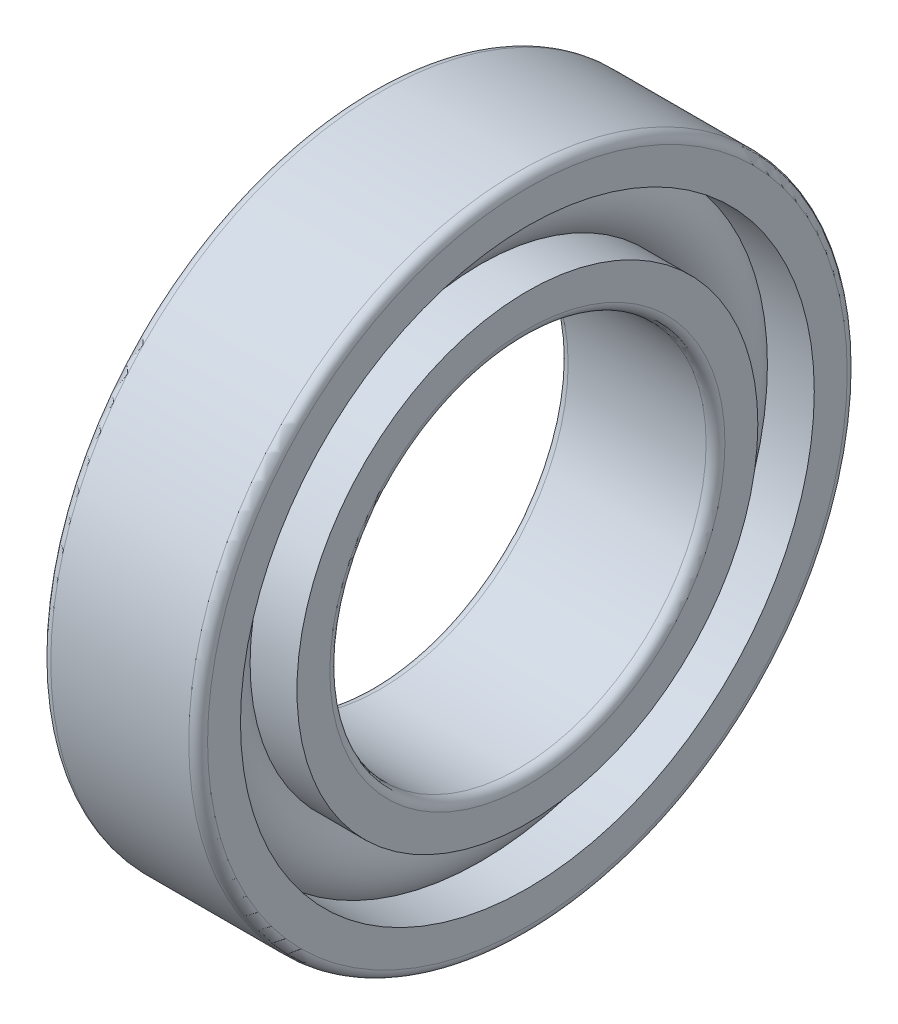
SolidWorks part; units mm, degrees
ref_plane "Plane1" through (0, 0, 0) normal (0, 0, 1) x (1, 0, 0)
ref_plane "Plane2" through (0, 0, 0) normal (0, 1, 0) x (1, 0, 0)
ref_plane "Plane3" through (0, 0, 0) normal (1, 0, 0) x (0, 0, -1)
sketch "Clipboard" plane through (0, 0, 0) normal (0, 0, 1) x (1, 0, 0)
  line L0 (-10, 0) -> (10, 0) construction
  line L1 (0, 0) -> (22.3471, -0.7804)
  line L2 (0, 0) -> (8.245, 0.2879)
  line L3 (0, 0) -> (22.3471, -0.7804)
  line L4 (0, 0) -> (-22.3573, -0.3902)
sketch "CagSpiSke" plane through (0, 0, 0) normal (0, 0, 1) x (1, 0, 0)
  line L0 (0.135, 8.025) -> (0.135, 8.475)
  line L1 (0.135, 8.475) -> (-0.135, 8.475)
  line L2 (-0.135, 8.475) -> (-0.135, 8.025)
  line L3 (-0.135, 8.025) -> (0.135, 8.025)
  line L4 (-20.6375, 0) -> (20.6375, 0) construction
  line L5 (0, 0) -> (0, 23.7692) construction
revolve "CageSpine" add sketch "CagSpiSke" angle 0.001 about L4 reverse direction yes
ref_axis "Axis1" through (-50, 0, 0) along (1, 0, 0)
sketch "CagBalSke" plane through (0, 0, 0) normal (0, 0, 1) x (1, 0, 0)
  line L0 (-1.485, 8.25) -> (1.485, 8.25)
  line L1 (-1.905, 8.25) -> (1.905, 8.25) construction
  line L2 (-10, 0) -> (10, 0) construction
  line L3 (0, 0) -> (0, 24) construction
  arc A0 (1.485, 8.25) -> (-1.485, 8.25) centre (0, 8.25) cw
revolve "CageBall" [suppressed] add sketch "CagBalSke" angle 360 about L1 reverse direction yes
pattern_circular "CageBalls" [suppressed] count 2 every 180 about axis through (-50, 0, 0) along (1, 0, 0)
sketch "CagTrmODSke" plane through (0, 0, 0) normal (0, 0, 1) x (1, 0, 0)
  line L0 (1.486, 8.475) -> (1.486, 9.736)
  line L1 (1.486, 9.736) -> (-1.486, 9.736)
  line L2 (-1.486, 9.736) -> (-1.486, 8.475)
  line L3 (-1.486, 8.475) -> (1.486, 8.475)
  line L4 (-20.6375, 0) -> (20.6375, 0) construction
  line L5 (0, 0) -> (0, 25) construction
revolve "CageTrimOD" [suppressed] cut sketch "CagTrmODSke" angle 360 about L4 reverse direction yes
sketch "CagTrmIDSke" plane through (0, 0, 0) normal (0, 0, 1) x (1, 0, 0)
  line L0 (1.486, 6.766) -> (1.486, 8.025)
  line L1 (1.486, 8.025) -> (-1.486, 8.025)
  line L2 (-1.486, 8.025) -> (-1.486, 6.766)
  line L3 (-1.486, 6.766) -> (1.486, 6.766)
  line L4 (-20.6375, 0) -> (20.6375, 0) construction
  line L5 (0, 0) -> (0, 25) construction
revolve "CageTrimID" [suppressed] cut sketch "CagTrmIDSke" angle 360 about L4 reverse direction yes
sketch "BalSimSke" plane through (0, 0, 0) normal (0, 0, 1) x (1, 0, 0)
  line L0 (-10, 0) -> (10, 0) construction
  line L1 (-10, 8.25) -> (10, 8.25) construction
  line L2 (0, 0) -> (0, 23) construction
  circle A0 centre (0, 8.25) radius 1.35
revolve "BallsSimplified" add sketch "BalSimSke" angle 360 about L0
sketch "BalDetSke" plane through (0, 0, 0) normal (0, 0, 1) x (1, 0, 0)
  line L0 (-1.35, 8.25) -> (1.35, 8.25)
  line L1 (-1.905, 8.25) -> (1.905, 8.25) construction
  line L2 (0, 0) -> (0, 25) construction
  arc A0 (1.35, 8.25) -> (-1.35, 8.25) centre (0, 8.25) cw
revolve "BallDetailed" [suppressed] add sketch "BalDetSke" angle 360 about L1 reverse direction yes
sketch "InnRacSke" plane through (0, 0, 0) normal (0, 0, 1) x (1, 0, 0)
  line L0 (-0.9724, 7.35) -> (-2.5, 7.35)
  line L1 (-2.5, 7.35) -> (-2.5, 6.3)
  line L2 (-2.2, 6) -> (2.2, 6)
  line L3 (2.5, 6.3) -> (2.5, 7.35)
  line L4 (2.5, 7.35) -> (0.9724, 7.35)
  line L5 (-20.6375, 0) -> (20.6375, 0) construction
  line L6 (0, 0) -> (0, 30) construction
  arc A0 (-2.5, 6.3) -> (-2.2, 6) centre (-2.2, 6.3) ccw
  arc A1 (2.2, 6) -> (2.5, 6.3) centre (2.2, 6.3) ccw
  arc A2 (0.9724, 7.35) -> (-0.9724, 7.35) centre (0, 8.25) cw
revolve "InnerRace" add sketch "InnRacSke" angle 360 about L5 reverse direction yes
sketch "OutRacSke" plane through (0, 0, 0) normal (0, 0, 1) x (1, 0, 0)
  line L0 (-0.9724, 9.15) -> (-2.5, 9.15)
  line L1 (-2.5, 9.15) -> (-2.5, 10.2)
  line L2 (-2.2, 10.5) -> (2.2, 10.5)
  line L3 (2.5, 10.2) -> (2.5, 9.15)
  line L4 (2.5, 9.15) -> (0.9724, 9.15)
  line L5 (-20.6375, 0) -> (20.6375, 0) construction
  line L6 (0, 0) -> (0, 30) construction
  arc A0 (-2.5, 10.2) -> (-2.2, 10.5) centre (-2.2, 10.2) cw
  arc A1 (2.2, 10.5) -> (2.5, 10.2) centre (2.2, 10.2) cw
  arc A2 (0.9724, 9.15) -> (-0.9724, 9.15) centre (0, 8.25) ccw
revolve "OuterRace" add sketch "OutRacSke" angle 360 about L5 reverse direction yes
pattern_circular "BallsDetailed" [suppressed] count 2 every 180 about axis through (-50, 0, 0) along (1, 0, 0)
equation "\"BallCLRad@Clipboard\" = ( \"OD@OutRacSke\" + \"ID@InnRacSke\" ) / 4"
equation "\"BallCLRad@BalSimSke\" = \"BallCLRad@Clipboard\""
equation "\"BallCLRad@BalDetSke\" = \"BallCLRad@Clipboard\""
equation "\"BallCLRad@InnRacSke\" = \"BallCLRad@Clipboard\""
equation "\"BallCLRad@OutRacSke\" = \"BallCLRad@Clipboard\""
equation "\"Ball_diameter@InnRacSke\" = \"Ball_diameter@BalDetSke\" - 0.05"
equation "\"Ball_diameter@OutRacSke\" = \"Ball_diameter@BalDetSke\" - 0.05"
equation "\"Ball_diameter@BalSimSke\" = \"Ball_diameter@BalDetSke\""
equation "\"Width@OutRacSke\" = \"Width@InnRacSke\""
equation "\"Fillet_radius@OutRacSke\" = \"Fillet_radius@InnRacSke\""
equation "\"Max_count@Clipboard\" = int( 3.14159265 / atn(( \"Ball_diameter@BalDetSke\" / 2) / sqr( \"BallCLRad@Clipboard\"  *  \"BallCLRad@Clipboard\" - ( \"Ball_diameter@BalDetSke\" / 2) *  ( \"Ball_diameter@BalDetSke\" / 2))))"
equation "\"Max_count@Clipboard\" = ((sgn( \"Max_count@Clipboard\" - \"Count@Clipboard\" )-1)*( \"Max_count@Clipboard\" - \"Count@Clipboard\" ))/-2+ \"Count@Clipboard\""
equation "\"Count@BallsDetailed\" = int( \"Show_count@Clipboard\" ) "
equation "\"Count@BallsDetailed\" = ((sgn( \"Count@BallsDetailed\" - \"Max_count@Clipboard\" )-1)*( \"Count@BallsDetailed\" - \"Max_count@Clipboard\" ))/-2+ \"Max_count@Clipboard\""
equation "\"Count@BallsDetailed\" = ((sgn( \"Count@BallsDetailed\" - \"Min_count@Clipboard\" )+1)*( \"Count@BallsDetailed\" - \"Min_count@Clipboard\"))/2 +\"Min_count@Clipboard\""
equation "\"Angle@BallsDetailed\" = 360.0 / \"Max_count@Clipboard\""
equation "\"BallCLRad@CagBalSke\" = \"BallCLRad@Clipboard\""
equation "\"Count@CageBalls\" = \"Count@BallsDetailed\""
equation "\"Angle@CageBalls\" = \"Angle@BallsDetailed\""
equation "\"Angle@CageSpine\" =  \"Angle@CageBalls\" * ( \"Count@CageBalls\" -1 + int( \"Count@CageBalls\" / \"Max_count@Clipboard\" ) )  + 0.001 -  int( \"Count@CageBalls\" / \"Max_count@Clipboard\" ) * 0.001"
equation "\"Angle@CageSpine\" =  \"Angle@CageSpine\" * int( \"Min_count@Clipboard\" / 2) + int(1 / \"Min_count@Clipboard\")  * 0.001"
equation "\"CageWallOD@CagBalSke\" =  \"Ball_diameter@BalDetSke\" * 1.1"
equation "\"Thickness@CagSpiSke\" =  \"Ball_diameter@BalDetSke\" * 0.1"
equation "\"OD@CagTrmODSke\" = \"BallCLRad@Clipboard\" * 2 + \"CageWallOD@CagBalSke\" + 0.002"
equation "\"ID@CagTrmODSke\" = \"BallCLRad@Clipboard\" * 2 + \"Ball_diameter@BalDetSke\" / 6"
equation "\"OD@CagTrmIDSke\" = \"BallCLRad@Clipboard\" * 2 - \"Ball_diameter@BalDetSke\" / 6"
equation "\"ID@CagTrmIDSke\" = \"BallCLRad@Clipboard\" * 2 - \"CageWallOD@CagBalSke\" + 0.002"
equation "\"OD@CagSpiSke\" = \"ID@CagTrmODSke\""
equation "\"ID@CagSpiSke\" = \"OD@CagTrmIDSke\""
equation "\"Width@CagTrmODSke\" = \"CageWallOD@CagBalSke\" + 0.002"
equation "\"Width@CagTrmIDSke\" = \"CageWallOD@CagBalSke\" + 0.002"
